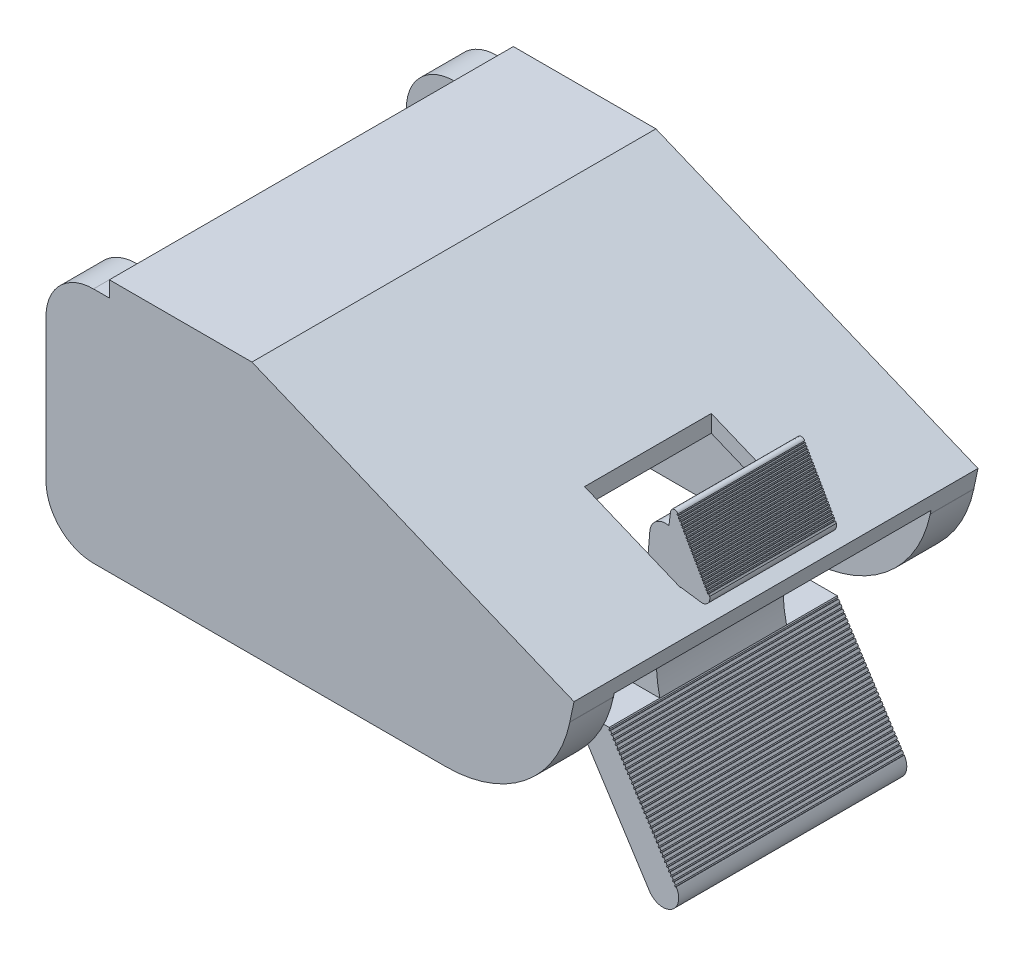
SolidWorks part; units mm, degrees
ref_plane "Plano frontal" through (0, 0, 0) normal (0, 0, 1) x (1, 0, 0)
ref_plane "Plano superior" through (0, 0, 0) normal (0, 1, 0) x (1, 0, 0)
ref_plane "Plano direito" through (0, 0, 0) normal (1, 0, 0) x (0, 0, -1)
ref_plane "Plano1" through (0, 0, -40.4876) normal (0, 0, 1) x (1, 0, 0)
sketch "Esboço1" plane through (0, 0, -40.4876) normal (0, 0, 1) x (1, 0, 0)
  line L0 (79.375, -65.0875) -> (150.0006, -65.0875)
  line L1 (174.849, -44.9523) -> (174.849, -44.8992)
  line L2 (174.849, -44.8992) -> (175.6854, -40.9517)
  line L3 (175.6854, -40.9517) -> (111.125, -14.2875)
  line L4 (111.125, -14.2875) -> (82.55, -14.2875)
  line L5 (82.55, -14.2875) -> (82.55, -17.4625)
  line L6 (82.55, -17.4625) -> (79.375, -17.4625)
  line L7 (69.85, -26.9875) -> (69.85, -55.5625)
  arc A0 (69.85, -55.5625) -> (79.375, -65.0875) centre (79.375, -55.5625) ccw
  arc A1 (150.0006, -65.0875) -> (174.849, -44.9523) centre (150.0006, -39.6875) ccw
  arc A2 (79.375, -17.4625) -> (69.85, -26.9875) centre (79.375, -26.9875) ccw
extrude "Ressalto-extrusão1" add sketch "Esboço1" along normal blind 3.175
ref_plane "Plano2" through (0, 0, 0) normal (0, 0, 1) x (1, 0, 0)
sketch "Esboço2" plane through (0, 0, 0) normal (0, 0, 1) x (1, 0, 0)
  line L0 (79.375, -65.0875) -> (150.0006, -65.0875)
  line L1 (174.849, -44.9523) -> (174.849, -44.8992)
  line L2 (174.849, -44.8992) -> (175.6854, -40.9517)
  line L3 (175.6854, -40.9517) -> (111.125, -14.2875)
  line L4 (111.125, -14.2875) -> (82.55, -14.2875)
  line L5 (82.55, -14.2875) -> (82.55, -17.4625)
  line L6 (82.55, -17.4625) -> (79.375, -17.4625)
  line L7 (69.85, -26.9875) -> (69.85, -55.5625)
  arc A0 (69.85, -55.5625) -> (79.375, -65.0875) centre (79.375, -55.5625) ccw
  arc A1 (150.0006, -65.0875) -> (174.849, -44.9523) centre (150.0006, -39.6875) ccw
  arc A2 (79.375, -17.4625) -> (69.85, -26.9875) centre (79.375, -26.9875) ccw
extrude "Ressalto-extrusão2" add sketch "Esboço2" against normal blind 37.3126 and the other way blind 37.3126
ref_plane "Plano3" through (0, 0, 40.4876) normal (0, 0, 1) x (1, 0, 0)
sketch "Esboço3" plane through (0, 0, 40.4876) normal (0, 0, 1) x (1, 0, 0)
  line L0 (79.375, -65.0875) -> (150.0006, -65.0875)
  line L1 (174.849, -44.9523) -> (174.849, -44.8992)
  line L2 (174.849, -44.8992) -> (175.6854, -40.9517)
  line L3 (175.6854, -40.9517) -> (111.125, -14.2875)
  line L4 (111.125, -14.2875) -> (82.55, -14.2875)
  line L5 (82.55, -14.2875) -> (82.55, -17.4625)
  line L6 (82.55, -17.4625) -> (79.375, -17.4625)
  line L7 (69.85, -26.9875) -> (69.85, -55.5625)
  arc A0 (69.85, -55.5625) -> (79.375, -65.0875) centre (79.375, -55.5625) ccw
  arc A1 (150.0006, -65.0875) -> (174.849, -44.9523) centre (150.0006, -39.6875) ccw
  arc A2 (79.375, -17.4625) -> (69.85, -26.9875) centre (79.375, -26.9875) ccw
extrude "Ressalto-extrusão3" add sketch "Esboço3" against normal blind 3.175
ref_plane "Plano4" through (0, 0, 0) normal (0, 0, 1) x (1, 0, 0)
sketch "Esboço4" plane through (0, 0, 0) normal (0, 0, 1) x (1, 0, 0)
  line L0 (79.375, -65.0875) -> (150.0006, -65.0875)
  line L1 (175.0128, -44.1091) -> (110.4951, -17.4625)
  line L2 (110.4951, -17.4625) -> (79.375, -17.4625)
  line L3 (69.85, -26.9875) -> (69.85, -55.5625)
  arc A0 (69.85, -55.5625) -> (79.375, -65.0875) centre (79.375, -55.5625) ccw
  arc A1 (150.0006, -65.0875) -> (175.0128, -44.1091) centre (150.0006, -39.6875) ccw
  arc A2 (79.375, -17.4625) -> (69.85, -26.9875) centre (79.375, -26.9875) ccw
extrude "Corte-extrusão1" cut sketch "Esboço4" against normal blind 31.75 and the other way blind 31.75
ref_plane "Plano5" through (0, 0, 0) normal (0, 0, 1) x (1, 0, 0)
sketch "Esboço5" plane through (0, 0, 0) normal (0, 0, 1) x (1, 0, 0)
  line L0 (162.7188, -36.068) -> (169.1536, -38.7257)
  line L1 (169.1536, -38.7257) -> (169.2592, -38.1762)
  line L2 (169.2592, -38.1762) -> (173.2099, -38.7353)
  line L3 (175.0976, -36.8814) -> (174.905, -36.5436)
  line L4 (174.905, -36.5436) -> (174.6844, -36.6694)
  line L5 (174.6844, -36.6694) -> (174.5586, -36.4487)
  line L6 (174.5586, -36.4487) -> (174.7792, -36.3229)
  line L7 (174.7792, -36.3229) -> (174.6534, -36.1022)
  line L8 (174.6534, -36.1022) -> (174.4328, -36.228)
  line L9 (174.4328, -36.228) -> (174.307, -36.0074)
  line L10 (174.307, -36.0074) -> (174.5276, -35.8816)
  line L11 (174.5276, -35.8816) -> (174.4018, -35.6609)
  line L12 (174.4018, -35.6609) -> (174.1812, -35.7867)
  line L13 (174.1812, -35.7867) -> (174.0554, -35.5661)
  line L14 (174.0554, -35.5661) -> (174.276, -35.4403)
  line L15 (174.276, -35.4403) -> (174.1502, -35.2196)
  line L16 (174.1502, -35.2196) -> (173.9296, -35.3454)
  line L17 (173.9296, -35.3454) -> (173.8038, -35.1248)
  line L18 (173.8038, -35.1248) -> (174.0244, -34.999)
  line L19 (174.0244, -34.999) -> (173.8986, -34.7783)
  line L20 (173.8986, -34.7783) -> (173.678, -34.9041)
  line L21 (173.678, -34.9041) -> (173.5522, -34.6834)
  line L22 (173.5522, -34.6834) -> (173.7728, -34.5576)
  line L23 (173.7728, -34.5576) -> (173.647, -34.337)
  line L24 (173.647, -34.337) -> (173.4264, -34.4628)
  line L25 (173.4264, -34.4628) -> (173.3006, -34.2421)
  line L26 (173.3006, -34.2421) -> (173.5212, -34.1163)
  line L27 (173.5212, -34.1163) -> (173.3954, -33.8957)
  line L28 (173.3954, -33.8957) -> (173.1748, -34.0215)
  line L29 (173.1748, -34.0215) -> (173.0489, -33.8008)
  line L30 (173.0489, -33.8008) -> (173.2696, -33.675)
  line L31 (173.2696, -33.675) -> (173.1438, -33.4544)
  line L32 (173.1438, -33.4544) -> (172.9231, -33.5802)
  line L33 (172.9231, -33.5802) -> (172.7973, -33.3595)
  line L34 (172.7973, -33.3595) -> (173.018, -33.2337)
  line L35 (173.018, -33.2337) -> (172.8922, -33.013)
  line L36 (172.8922, -33.013) -> (172.6715, -33.1388)
  line L37 (172.6715, -33.1388) -> (172.5457, -32.9182)
  line L38 (172.5457, -32.9182) -> (172.7664, -32.7924)
  line L39 (172.7664, -32.7924) -> (172.6406, -32.5717)
  line L40 (172.6406, -32.5717) -> (172.4199, -32.6975)
  line L41 (172.4199, -32.6975) -> (172.2941, -32.4769)
  line L42 (172.2941, -32.4769) -> (172.5148, -32.3511)
  line L43 (172.5148, -32.3511) -> (172.389, -32.1304)
  line L44 (172.389, -32.1304) -> (172.1683, -32.2562)
  line L45 (172.1683, -32.2562) -> (172.0425, -32.0356)
  line L46 (172.0425, -32.0356) -> (172.2632, -31.9098)
  line L47 (172.2632, -31.9098) -> (172.1374, -31.6891)
  line L48 (172.1374, -31.6891) -> (171.9167, -31.8149)
  line L49 (171.9167, -31.8149) -> (171.7909, -31.5942)
  line L50 (171.7909, -31.5942) -> (172.0116, -31.4684)
  line L51 (172.0116, -31.4684) -> (171.8858, -31.2478)
  line L52 (171.8858, -31.2478) -> (171.6651, -31.3736)
  line L53 (171.6651, -31.3736) -> (171.5393, -31.1529)
  line L54 (171.5393, -31.1529) -> (171.76, -31.0271)
  line L55 (171.76, -31.0271) -> (171.6342, -30.8065)
  line L56 (171.6342, -30.8065) -> (171.4135, -30.9323)
  line L57 (171.4135, -30.9323) -> (171.2877, -30.7116)
  line L58 (171.2877, -30.7116) -> (171.5084, -30.5858)
  line L59 (171.5084, -30.5858) -> (171.3826, -30.3652)
  line L60 (171.3826, -30.3652) -> (171.1619, -30.491)
  line L61 (171.1619, -30.491) -> (171.0361, -30.2703)
  line L62 (171.0361, -30.2703) -> (171.2568, -30.1445)
  line L63 (171.2568, -30.1445) -> (171.131, -29.9238)
  line L64 (171.131, -29.9238) -> (170.9103, -30.0496)
  line L65 (170.9103, -30.0496) -> (170.7845, -29.829)
  line L66 (170.7845, -29.829) -> (171.0052, -29.7032)
  line L67 (171.0052, -29.7032) -> (170.8794, -29.4825)
  line L68 (170.8794, -29.4825) -> (170.6587, -29.6083)
  line L69 (170.6587, -29.6083) -> (170.5329, -29.3877)
  line L70 (170.5329, -29.3877) -> (170.7536, -29.2619)
  line L71 (170.7536, -29.2619) -> (170.6278, -29.0412)
  line L72 (170.6278, -29.0412) -> (170.4071, -29.167)
  line L73 (170.4071, -29.167) -> (170.2813, -28.9464)
  line L74 (170.2813, -28.9464) -> (170.5019, -28.8206)
  line L75 (170.5019, -28.8206) -> (170.3761, -28.5999)
  line L76 (170.3761, -28.5999) -> (170.1555, -28.7257)
  line L77 (170.1555, -28.7257) -> (170.0297, -28.505)
  line L78 (170.0297, -28.505) -> (170.2503, -28.3792)
  line L79 (170.2503, -28.3792) -> (170.1245, -28.1586)
  line L80 (170.1245, -28.1586) -> (169.9039, -28.2844)
  line L81 (169.9039, -28.2844) -> (169.7781, -28.0637)
  line L82 (169.7781, -28.0637) -> (169.9987, -27.9379)
  line L83 (169.9987, -27.9379) -> (169.8729, -27.7173)
  line L84 (169.8729, -27.7173) -> (169.6523, -27.8431)
  line L85 (169.6523, -27.8431) -> (169.5265, -27.6224)
  line L86 (169.5265, -27.6224) -> (169.7471, -27.4966)
  line L87 (169.7471, -27.4966) -> (169.6213, -27.2759)
  line L88 (169.6213, -27.2759) -> (169.4007, -27.4018)
  line L89 (169.4007, -27.4018) -> (169.2749, -27.1811)
  line L90 (169.2749, -27.1811) -> (169.4955, -27.0553)
  line L91 (169.4955, -27.0553) -> (169.3697, -26.8346)
  line L92 (169.3697, -26.8346) -> (169.1491, -26.9604)
  line L93 (169.1491, -26.9604) -> (169.0233, -26.7398)
  line L94 (169.0233, -26.7398) -> (169.2439, -26.614)
  line L95 (169.2439, -26.614) -> (169.1181, -26.3933)
  line L96 (169.1181, -26.3933) -> (168.8975, -26.5191)
  line L97 (168.8975, -26.5191) -> (168.7717, -26.2985)
  line L98 (168.7717, -26.2985) -> (168.9923, -26.1727)
  line L99 (168.9923, -26.1727) -> (168.8665, -25.952)
  line L100 (168.8665, -25.952) -> (168.6459, -26.0778)
  line L101 (168.6459, -26.0778) -> (168.5201, -25.8571)
  line L102 (168.5201, -25.8571) -> (168.7407, -25.7313)
  line L103 (167.2584, -26.0839) -> (166.9184, -28.6848)
  line L104 (163.0963, -31.5277) -> (162.7188, -36.068)
  arc A0 (173.2099, -38.7353) -> (175.0976, -36.8814) centre (173.5389, -37.1823) ccw
  arc A1 (168.7407, -25.7313) -> (167.2641, -26.0216) centre (168.0512, -26.1245) ccw
  arc A2 (167.2641, -26.0216) -> (167.2584, -26.0839) centre (168.0512, -26.1245) ccw
  arc A3 (166.9184, -28.6848) -> (163.0963, -31.5277) centre (166.2603, -31.7908) ccw
extrude "Ressalto-extrusão4" add sketch "Esboço5" against normal blind 12.7 and the other way blind 12.7
ref_plane "Plano6" through (0, 0, 0) normal (0, 0, 1) x (1, 0, 0)
sketch "Esboço6" plane through (0, 0, 0) normal (0, 0, 1) x (1, 0, 0)
  line L0 (158.0492, -59.5312) -> (165.1, -59.5312)
  line L1 (169.1536, -38.7257) -> (162.7188, -36.068)
  arc A0 (162.7188, -36.068) -> (158.0492, -59.5312) centre (178.6703, -51.4389) ccw
  arc A1 (165.1, -59.5312) -> (169.1536, -38.7257) centre (190.154, -53.615) cw
extrude "Ressalto-extrusão5" add sketch "Esboço6" against normal blind 12.7 and the other way blind 12.7
ref_plane "Plano7" through (0, 0, 0) normal (0, 0, 1) x (1, 0, 0)
sketch "Esboço7" plane through (0, 0, 0) normal (0, 0, 1) x (1, 0, 0)
  line L0 (159.6633, -62.8166) -> (173.1926, -83.9161)
  line L1 (178.5362, -80.4855) -> (178.3224, -80.6226)
  line L2 (178.3224, -80.6226) -> (178.1853, -80.4088)
  line L3 (178.1853, -80.4088) -> (178.3991, -80.2717)
  line L4 (178.3991, -80.2717) -> (178.1249, -79.844)
  line L5 (178.1249, -79.844) -> (177.911, -79.9812)
  line L6 (177.911, -79.9812) -> (177.7739, -79.7673)
  line L7 (177.7739, -79.7673) -> (177.9878, -79.6302)
  line L8 (177.9878, -79.6302) -> (177.7136, -79.2026)
  line L9 (177.7136, -79.2026) -> (177.4997, -79.3397)
  line L10 (177.4997, -79.3397) -> (177.3626, -79.1259)
  line L11 (177.3626, -79.1259) -> (177.5764, -78.9888)
  line L12 (177.5764, -78.9888) -> (177.3022, -78.5611)
  line L13 (177.3022, -78.5611) -> (177.0884, -78.6982)
  line L14 (177.0884, -78.6982) -> (176.9513, -78.4844)
  line L15 (176.9513, -78.4844) -> (177.1651, -78.3473)
  line L16 (177.1651, -78.3473) -> (176.8909, -77.9197)
  line L17 (176.8909, -77.9197) -> (176.6771, -78.0568)
  line L18 (176.6771, -78.0568) -> (176.54, -77.843)
  line L19 (176.54, -77.843) -> (176.7538, -77.7059)
  line L20 (176.7538, -77.7059) -> (176.4796, -77.2782)
  line L21 (176.4796, -77.2782) -> (176.2658, -77.4153)
  line L22 (176.2658, -77.4153) -> (176.1287, -77.2015)
  line L23 (176.1287, -77.2015) -> (176.3425, -77.0644)
  line L24 (176.3425, -77.0644) -> (176.0683, -76.6368)
  line L25 (176.0683, -76.6368) -> (175.8545, -76.7739)
  line L26 (175.8545, -76.7739) -> (175.7174, -76.56)
  line L27 (175.7174, -76.56) -> (175.9312, -76.4229)
  line L28 (175.9312, -76.4229) -> (175.657, -75.9953)
  line L29 (175.657, -75.9953) -> (175.4432, -76.1324)
  line L30 (175.4432, -76.1324) -> (175.3061, -75.9186)
  line L31 (175.3061, -75.9186) -> (175.5199, -75.7815)
  line L32 (175.5199, -75.7815) -> (175.2457, -75.3539)
  line L33 (175.2457, -75.3539) -> (175.0319, -75.491)
  line L34 (175.0319, -75.491) -> (174.8948, -75.2771)
  line L35 (174.8948, -75.2771) -> (175.1086, -75.14)
  line L36 (175.1086, -75.14) -> (174.8344, -74.7124)
  line L37 (174.8344, -74.7124) -> (174.6206, -74.8495)
  line L38 (174.6206, -74.8495) -> (174.4835, -74.6357)
  line L39 (174.4835, -74.6357) -> (174.6973, -74.4986)
  line L40 (174.6973, -74.4986) -> (174.4231, -74.0709)
  line L41 (174.4231, -74.0709) -> (174.2092, -74.208)
  line L42 (174.2092, -74.208) -> (174.0721, -73.9942)
  line L43 (174.0721, -73.9942) -> (174.286, -73.8571)
  line L44 (174.286, -73.8571) -> (174.0117, -73.4295)
  line L45 (174.0117, -73.4295) -> (173.7979, -73.5666)
  line L46 (173.7979, -73.5666) -> (173.6608, -73.3528)
  line L47 (173.6608, -73.3528) -> (173.8746, -73.2157)
  line L48 (173.8746, -73.2157) -> (173.6004, -72.788)
  line L49 (173.6004, -72.788) -> (173.3866, -72.9251)
  line L50 (173.3866, -72.9251) -> (173.2495, -72.7113)
  line L51 (173.2495, -72.7113) -> (173.4633, -72.5742)
  line L52 (173.4633, -72.5742) -> (173.1891, -72.1466)
  line L53 (173.1891, -72.1466) -> (172.9753, -72.2837)
  line L54 (172.9753, -72.2837) -> (172.8382, -72.0699)
  line L55 (172.8382, -72.0699) -> (173.052, -71.9327)
  line L56 (173.052, -71.9327) -> (172.7778, -71.5051)
  line L57 (172.7778, -71.5051) -> (172.564, -71.6422)
  line L58 (172.564, -71.6422) -> (172.4269, -71.4284)
  line L59 (172.4269, -71.4284) -> (172.6407, -71.2913)
  line L60 (172.6407, -71.2913) -> (172.3665, -70.8637)
  line L61 (172.3665, -70.8637) -> (172.1527, -71.0008)
  line L62 (172.1527, -71.0008) -> (172.0156, -70.7869)
  line L63 (172.0156, -70.7869) -> (172.2294, -70.6498)
  line L64 (172.2294, -70.6498) -> (171.9552, -70.2222)
  line L65 (171.9552, -70.2222) -> (171.7414, -70.3593)
  line L66 (171.7414, -70.3593) -> (171.6043, -70.1455)
  line L67 (171.6043, -70.1455) -> (171.8181, -70.0084)
  line L68 (171.8181, -70.0084) -> (171.5439, -69.5807)
  line L69 (171.5439, -69.5807) -> (171.3301, -69.7178)
  line L70 (171.3301, -69.7178) -> (171.193, -69.504)
  line L71 (171.193, -69.504) -> (171.4068, -69.3669)
  line L72 (171.4068, -69.3669) -> (171.1326, -68.9393)
  line L73 (171.1326, -68.9393) -> (170.9188, -69.0764)
  line L74 (170.9188, -69.0764) -> (170.7816, -68.8626)
  line L75 (170.7816, -68.8626) -> (170.9955, -68.7255)
  line L76 (170.9955, -68.7255) -> (170.7213, -68.2978)
  line L77 (170.7213, -68.2978) -> (170.5074, -68.4349)
  line L78 (170.5074, -68.4349) -> (170.3703, -68.2211)
  line L79 (170.3703, -68.2211) -> (170.5842, -68.084)
  line L80 (170.5842, -68.084) -> (170.3099, -67.6564)
  line L81 (170.3099, -67.6564) -> (170.0961, -67.7935)
  line L82 (170.0961, -67.7935) -> (169.959, -67.5797)
  line L83 (169.959, -67.5797) -> (170.1728, -67.4426)
  line L84 (170.1728, -67.4426) -> (169.8986, -67.0149)
  line L85 (169.8986, -67.0149) -> (169.6848, -67.152)
  line L86 (169.6848, -67.152) -> (169.5477, -66.9382)
  line L87 (169.5477, -66.9382) -> (169.7615, -66.8011)
  line L88 (169.7615, -66.8011) -> (169.4873, -66.3735)
  line L89 (169.4873, -66.3735) -> (169.2735, -66.5106)
  line L90 (169.2735, -66.5106) -> (169.1364, -66.2967)
  line L91 (169.1364, -66.2967) -> (169.3502, -66.1596)
  line L92 (169.3502, -66.1596) -> (169.076, -65.732)
  line L93 (169.076, -65.732) -> (168.8622, -65.8691)
  line L94 (168.8622, -65.8691) -> (168.7251, -65.6553)
  line L95 (168.7251, -65.6553) -> (168.9389, -65.5182)
  line L96 (168.9389, -65.5182) -> (168.6647, -65.0905)
  line L97 (168.6647, -65.0905) -> (168.4509, -65.2276)
  line L98 (168.4509, -65.2276) -> (168.3138, -65.0138)
  line L99 (168.3138, -65.0138) -> (168.5276, -64.8767)
  line L100 (168.5276, -64.8767) -> (168.2534, -64.4491)
  line L101 (168.2534, -64.4491) -> (168.0396, -64.5862)
  line L102 (168.0396, -64.5862) -> (167.9025, -64.3724)
  line L103 (167.9025, -64.3724) -> (168.1163, -64.2353)
  line L104 (168.1163, -64.2353) -> (167.8421, -63.8076)
  line L105 (167.8421, -63.8076) -> (167.6283, -63.9447)
  line L106 (167.6283, -63.9447) -> (167.4912, -63.7309)
  line L107 (167.4912, -63.7309) -> (167.705, -63.5938)
  line L108 (167.705, -63.5938) -> (167.4308, -63.1662)
  line L109 (167.4308, -63.1662) -> (167.2169, -63.3033)
  line L110 (167.2169, -63.3033) -> (167.0798, -63.0895)
  line L111 (167.0798, -63.0895) -> (167.2937, -62.9524)
  line L112 (167.2937, -62.9524) -> (167.0195, -62.5247)
  line L113 (167.0195, -62.5247) -> (166.8056, -62.6618)
  line L114 (166.8056, -62.6618) -> (166.6685, -62.448)
  line L115 (166.6685, -62.448) -> (166.8823, -62.3109)
  line L116 (166.8823, -62.3109) -> (166.6081, -61.8833)
  line L117 (166.6081, -61.8833) -> (166.3943, -62.0204)
  line L118 (166.3943, -62.0204) -> (166.2572, -61.8065)
  line L119 (166.2572, -61.8065) -> (166.471, -61.6694)
  line L120 (166.471, -61.6694) -> (166.1968, -61.2418)
  line L121 (166.1968, -61.2418) -> (165.983, -61.3789)
  line L122 (165.983, -61.3789) -> (165.8459, -61.1651)
  line L123 (165.8459, -61.1651) -> (166.0597, -61.028)
  line L124 (166.0597, -61.028) -> (165.7855, -60.6003)
  line L125 (165.7855, -60.6003) -> (165.5717, -60.7374)
  line L126 (165.5717, -60.7374) -> (165.4346, -60.5236)
  line L127 (165.4346, -60.5236) -> (165.6484, -60.3865)
  line L128 (165.6484, -60.3865) -> (165.3742, -59.9589)
  line L129 (165.3742, -59.9589) -> (165.1604, -60.096)
  line L130 (165.1604, -60.096) -> (165.0233, -59.8822)
  line L131 (165.0233, -59.8822) -> (165.2371, -59.7451)
  line L132 (165.2371, -59.7451) -> (165.1, -59.5312)
  line L133 (165.1, -59.5312) -> (158.0492, -59.5312)
  arc A0 (158.0492, -59.5312) -> (159.6633, -62.8166) centre (178.6703, -51.4389) ccw
  arc A1 (173.1926, -83.9161) -> (178.5362, -80.4855) centre (175.8653, -82.2023) ccw
extrude "Ressalto-extrusão6" add sketch "Esboço7" against normal blind 22.86 and the other way blind 22.86
ref_plane "Plano8" through (0, 0, 0) normal (0, 0, 1) x (1, 0, 0)
sketch "Esboço8" plane through (0, 0, 0) normal (0, 0, 1) x (1, 0, 0)
  line L0 (150.0188, -30.2731) -> (150.0188, -34.2579)
  line L1 (150.0188, -34.2579) -> (162.7188, -39.5031)
  line L2 (162.7188, -39.5031) -> (162.7188, -35.5184)
  line L3 (162.7188, -35.5184) -> (150.0188, -30.2731)
extrude "Corte-extrusão2" cut sketch "Esboço8" against normal blind 12.7 and the other way blind 12.7
ref_plane "Plano9" through (0, 0, -31.75) normal (0, 0, 1) x (1, 0, 0)
sketch "Esboço9" plane through (0, 0, -31.75) normal (0, 0, 1) x (1, 0, 0)
  circle A0 centre (161.7438, -49.6213) radius 2.54
extrude "Ressalto-extrusão7" add sketch "Esboço9" along normal blind 63.5
